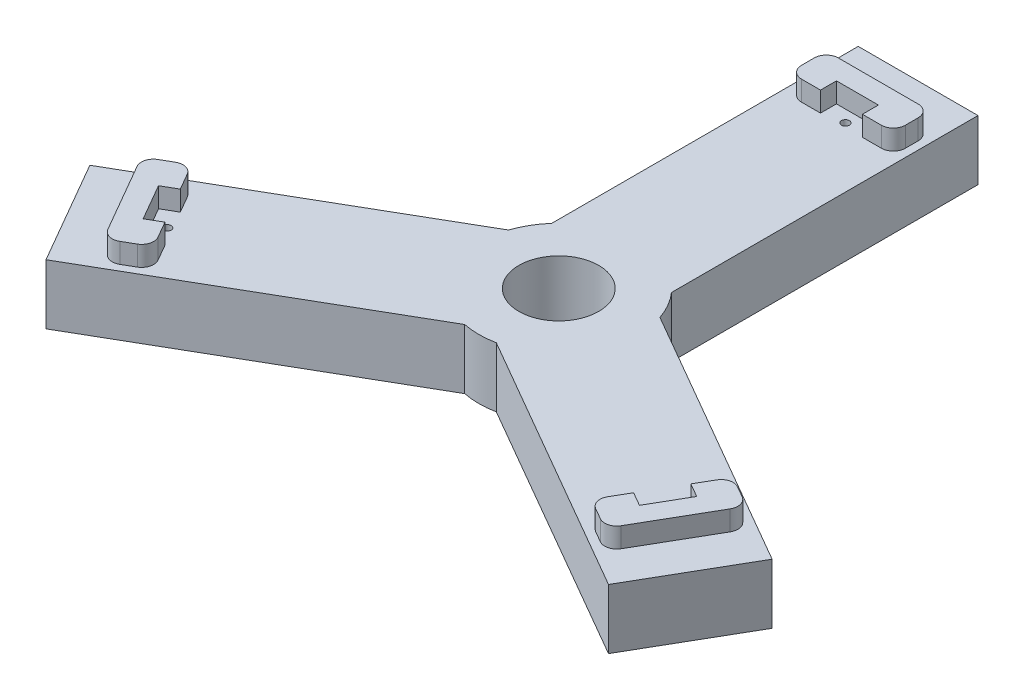
SolidWorks part; units mm, degrees
ref_plane "Front Plane" through (0, 0, 0) normal (0, 0, 1) x (1, 0, 0)
ref_plane "Top Plane" through (0, 0, 0) normal (0, 1, 0) x (1, 0, 0)
ref_plane "Right Plane" through (0, 0, 0) normal (1, 0, 0) x (0, 0, -1)
sketch "Sketch5" plane through (0, 0, 0) normal (0, 1, 0) x (1, 0, 0)
  circle A0 centre (0, 0) radius 20
  dimension "D1" = 40
extrude "Boss-Extrude2" add sketch "Sketch5" along normal blind 15
sketch "Sketch6" plane through (0, 0, 0) normal (0, 1, 0) x (1, 0, 0)
  line L0 (0, -11) -> (0, 11) construction
  line L1 (15, 0) -> (-15, 0)
  line L2 (15, 0) -> (15, 90)
  line L3 (15, 90) -> (-15, 90)
  line L4 (-15, 0) -> (-15, 90)
  dimension "D1" = 90
  dimension "D2" = 15
  dimension "D3" = 15
extrude "Boss-Extrude3" add sketch "Sketch6" along normal blind 15
pattern_circular "CirPattern1" count 3 over 360 about axis through (0, 15, 0) along (0, -1, 0) of "Boss-Extrude3"
sketch "Sketch7" plane through (0, 15, 0) normal (0, 1, 0) x (1, 0, 0)
  line L0 (0, -11) -> (0, 11) construction
  line L1 (-13, 80) -> (13, 80)
  line L2 (-13, 80) -> (-13, 70.8)
  line L3 (-13, 70.8) -> (-5.25, 70.8)
  line L4 (13, 80) -> (13, 70.8)
  line L5 (5.25, 70.8) -> (5.25, 74.8)
  line L6 (5.25, 74.8) -> (-5.25, 74.8)
  line L7 (-5.25, 74.8) -> (-5.25, 70.8)
  line L8 (-11, 0) -> (11, 0) construction
  line L9 (5.25, 70.8) -> (13, 70.8)
  point P8 (5.25, 72.8)
  dimension "D1" = 26
  dimension "D2" = 13
  dimension "D3" = 9.2
  dimension "D4" = 5.25
  dimension "D5" = 4
  dimension "D6" = 5.25
  dimension "D7" = 80
extrude "Boss-Extrude4" add sketch "Sketch7" along normal blind 5
fillet "Fillet1" radius 3 4 edges at (13, 17.5, -70.8) (13, 17.5, -80) (-13, 17.5, -70.8) (-13, 17.5, -80)
sketch "Sketch8" plane through (0, 15, 0) normal (0, 1, 0) x (1, 0, 0)
  line L0 (5.25, 70.8) -> (10, 70.8) construction
  circle A0 centre (0, 71.8) radius 1
  dimension "D1" = 2
  dimension "D2" = 1
extrude "Cut-Extrude1" cut sketch "Sketch8" against normal through all
sketch "Sketch9" plane through (0, 0, 0) normal (0, -1, 0) x (1, 0, 0)
  circle A0 centre (0, -71.8) radius 10
  dimension "D1" = 20
extrude "Cut-Extrude2" cut sketch "Sketch9" against normal blind 10 contours A0
pattern_circular "CirPattern4" count 3 over 360 about axis through (0, 15, 0) along (0, -1, 0) of "Boss-Extrude4", "Fillet1"
pattern_circular "CirPattern6" count 3 over 360 about axis through (0, 15, 0) along (0, -1, 0) of "Cut-Extrude1", "Cut-Extrude2"
sketch "Sketch10" plane through (0, 0, 0) normal (0, -1, 0) x (1, 0, 0)
  circle A0 centre (0, 0) radius 10
  dimension "D1" = 20
extrude "Cut-Extrude3" cut sketch "Sketch10" against normal through all
